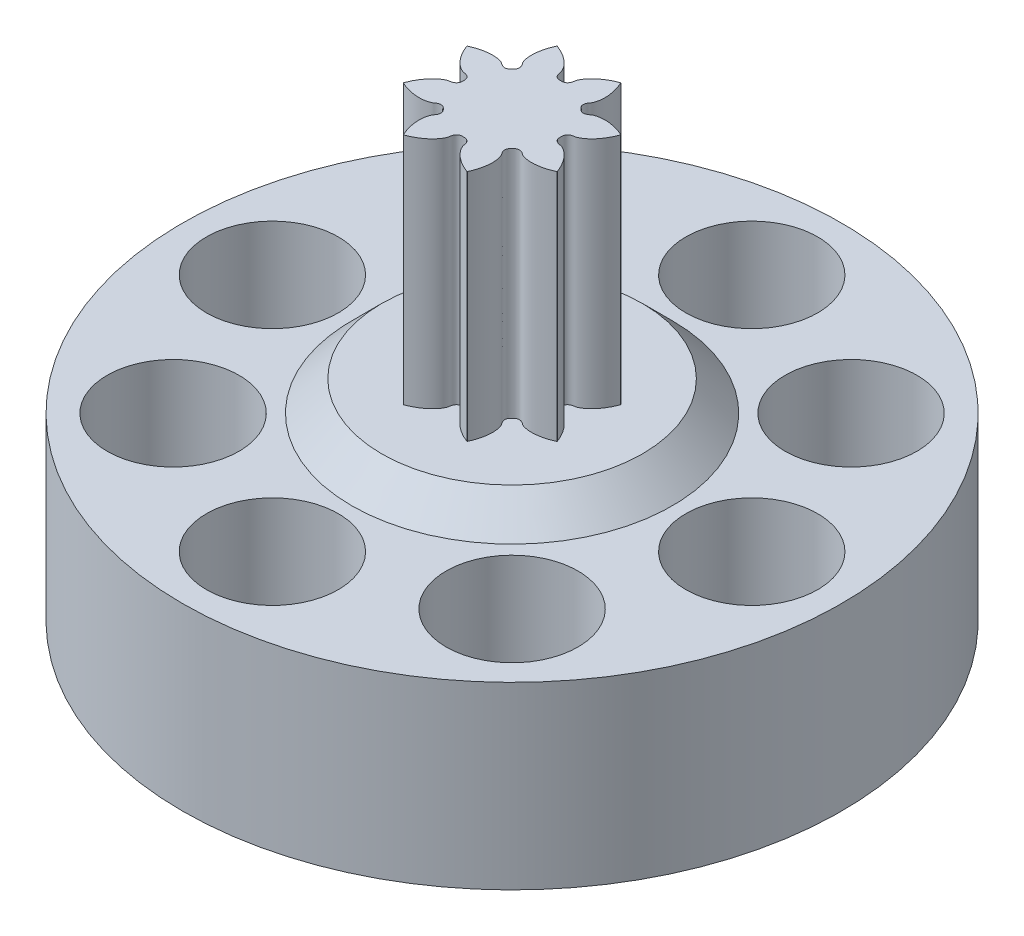
SolidWorks part; units mm, degrees
ref_plane "Front Plane" through (0, 0, 0) normal (0, 0, 1) x (1, 0, 0)
ref_plane "Top Plane" through (0, 0, 0) normal (0, 1, 0) x (1, 0, 0)
ref_plane "Right Plane" through (0, 0, 0) normal (1, 0, 0) x (0, 0, -1)
sketch "Sketch1" plane through (0, 0, 0) normal (0, 1, 0) x (1, 0, 0)
  circle A0 centre (0, 0) radius 11
  dimension "D1" = 22
extrude "Boss-Extrude1" add sketch "Sketch1" along normal mid plane 6
sketch "Sketch2" plane through (0, 3, 0) normal (0, 1, 0) x (1, 0, 0)
  circle A0 centre (0, 8) radius 1
  circle A1 centre (-5.6569, 5.6569) radius 1
  circle A2 centre (5.6569, 5.6569) radius 1
  circle A3 centre (-5.6569, -5.6569) radius 1
  circle A4 centre (5.6569, -5.6569) radius 1
  circle A5 centre (-8, 0) radius 1
  circle A6 centre (0, -8) radius 1
  circle A7 centre (8, 0) radius 1
  circle A8 centre (0, 0) radius 4
  circle A9 centre (0, 0) radius 11
sketch "Sketch5" plane through (0, 3, 0) normal (0, 1, 0) x (1, 0, 0)
  line L0 (2.5656, 1.0576) -> (2.562, 1.0663)
  line L1 (1.0663, 2.562) -> (1.0576, 2.5656)
  line L2 (-1.0576, 2.5656) -> (-1.0663, 2.562)
  line L3 (-2.562, 1.0663) -> (-2.5656, 1.0576)
  line L4 (-2.5656, -1.0576) -> (-2.562, -1.0663)
  line L5 (-1.0663, -2.562) -> (-1.0576, -2.5656)
  line L6 (1.0576, -2.5656) -> (1.0663, -2.562)
  line L7 (2.562, -1.0663) -> (2.5656, -1.0576)
  circle A1 centre (0, 0) radius 2.8
  spline S0 degree 3 poles (2.5656, 1.0576) (2.5467, 1.0063) (2.5127, 0.9243) (2.4586, 0.8162) (2.4108, 0.7326) (2.3616, 0.6567) (2.3117, 0.5883) (2.2618, 0.5274) (2.2125, 0.4736) (2.1645, 0.4267) (2.1184, 0.3865) (2.0746, 0.3524) (2.0339, 0.3241) (1.9966, 0.3012) (1.9632, 0.2831) (1.9342, 0.2695) (1.9099, 0.2596) (1.8905, 0.253) (1.8694, 0.2467) (1.8487, 0.2452) (1.828, 0.2423) (1.8074, 0.2387) (1.7821, 0.2325) (1.7521, 0.2221) (1.7278, 0.2103) (1.7086, 0.1983) (1.6939, 0.1875) (1.6793, 0.1746) (1.665, 0.1592) (1.6515, 0.1408) (1.6395, 0.1191) (1.6301, 0.0941) (1.6246, 0.0677) (1.6231, 0.036) (1.6249, 0) (1.6231, -0.036) (1.6246, -0.0677) (1.6301, -0.0941) (1.6395, -0.1191) (1.6515, -0.1408) (1.665, -0.1592) (1.6793, -0.1746) (1.6982, -0.1913) (1.7224, -0.2076) (1.7521, -0.2221) (1.7821, -0.2325) (1.8074, -0.2387) (1.828, -0.2423) (1.8487, -0.2452) (1.8694, -0.2467) (1.8905, -0.253) (1.9099, -0.2596) (1.9342, -0.2695) (1.9632, -0.2831) (1.9966, -0.3012) (2.0339, -0.3241) (2.0746, -0.3524) (2.1184, -0.3865) (2.1645, -0.4267) (2.2125, -0.4736) (2.2618, -0.5274) (2.3117, -0.5883) (2.3616, -0.6567) (2.4108, -0.7326) (2.4586, -0.8162) (2.5127, -0.9243) (2.5467, -1.0063) (2.5656, -1.0576) knots 0.018496 0.018496 0.018496 0.018496 0.071158 0.103928 0.134826 0.16385 0.191003 0.216283 0.23969 0.261224 0.280886 0.298676 0.314593 0.328637 0.340809 0.351108 0.359535 0.366089 0.37077 0.380767 0.385886 0.390938 0.400931 0.410975 0.421412 0.426928 0.432746 0.438959 0.445665 0.452957 0.460893 0.469469 0.478579 0.486756 0.5 0.513244 0.521421 0.530531 0.539107 0.547043 0.554335 0.561041 0.567254 0.578588 0.589025 0.599069 0.609062 0.614114 0.619233 0.62923 0.633911 0.640465 0.648892 0.659191 0.671363 0.685407 0.701324 0.719114 0.738776 0.76031 0.783717 0.808997 0.83615 0.865174 0.896072 0.928842 0.981504 0.981504 0.981504 0.981504
  spline S1 degree 3 poles (1.0663, 2.562) (1.0892, 2.5123) (1.1232, 2.4303) (1.1614, 2.3156) (1.1867, 2.2227) (1.2056, 2.1343) (1.2186, 2.0507) (1.2264, 1.9723) (1.2296, 1.8994) (1.2288, 1.8323) (1.2246, 1.7712) (1.2178, 1.7162) (1.209, 1.6673) (1.1988, 1.6248) (1.188, 1.5884) (1.1771, 1.5582) (1.1669, 1.534) (1.1579, 1.5157) (1.1474, 1.4963) (1.1339, 1.4806) (1.1212, 1.464) (1.1092, 1.4468) (1.0957, 1.4245) (1.0819, 1.396) (1.0731, 1.3704) (1.0679, 1.3484) (1.0652, 1.3304) (1.0639, 1.3109) (1.0647, 1.2899) (1.0682, 1.2673) (1.0751, 1.2435) (1.0861, 1.2192) (1.1009, 1.1966) (1.1223, 1.1732) (1.149, 1.149) (1.1732, 1.1223) (1.1966, 1.1009) (1.2192, 1.0861) (1.2435, 1.0751) (1.2673, 1.0682) (1.2899, 1.0647) (1.3109, 1.0639) (1.3361, 1.0655) (1.3647, 1.0711) (1.396, 1.0819) (1.4245, 1.0957) (1.4468, 1.1092) (1.464, 1.1212) (1.4806, 1.1339) (1.4963, 1.1474) (1.5157, 1.1579) (1.534, 1.1669) (1.5582, 1.1771) (1.5884, 1.188) (1.6248, 1.1988) (1.6673, 1.209) (1.7162, 1.2178) (1.7712, 1.2246) (1.8323, 1.2288) (1.8994, 1.2296) (1.9723, 1.2264) (2.0507, 1.2186) (2.1343, 1.2056) (2.2227, 1.1867) (2.3156, 1.1614) (2.4303, 1.1232) (2.5123, 1.0892) (2.562, 1.0663) knots 0.018496 0.018496 0.018496 0.018496 0.071158 0.103928 0.134826 0.16385 0.191003 0.216283 0.23969 0.261224 0.280886 0.298676 0.314593 0.328637 0.340809 0.351108 0.359535 0.366089 0.37077 0.380767 0.385886 0.390938 0.400931 0.410975 0.421412 0.426928 0.432746 0.438959 0.445665 0.452957 0.460893 0.469469 0.478579 0.486756 0.5 0.513244 0.521421 0.530531 0.539107 0.547043 0.554335 0.561041 0.567254 0.578588 0.589025 0.599069 0.609062 0.614114 0.619233 0.62923 0.633911 0.640465 0.648892 0.659191 0.671363 0.685407 0.701324 0.719114 0.738776 0.76031 0.783717 0.808997 0.83615 0.865174 0.896072 0.928842 0.981504 0.981504 0.981504 0.981504
  spline S2 degree 3 poles (-1.0576, 2.5656) (-1.0063, 2.5467) (-0.9243, 2.5127) (-0.8162, 2.4586) (-0.7326, 2.4108) (-0.6567, 2.3616) (-0.5883, 2.3117) (-0.5274, 2.2618) (-0.4736, 2.2125) (-0.4267, 2.1645) (-0.3865, 2.1184) (-0.3524, 2.0746) (-0.3241, 2.0339) (-0.3012, 1.9966) (-0.2831, 1.9632) (-0.2695, 1.9342) (-0.2596, 1.9099) (-0.253, 1.8905) (-0.2467, 1.8694) (-0.2452, 1.8487) (-0.2423, 1.828) (-0.2387, 1.8074) (-0.2325, 1.7821) (-0.2221, 1.7521) (-0.2103, 1.7278) (-0.1983, 1.7086) (-0.1875, 1.6939) (-0.1746, 1.6793) (-0.1592, 1.665) (-0.1408, 1.6515) (-0.1191, 1.6395) (-0.0941, 1.6301) (-0.0677, 1.6246) (-0.036, 1.6231) (0, 1.6249) (0.036, 1.6231) (0.0677, 1.6246) (0.0941, 1.6301) (0.1191, 1.6395) (0.1408, 1.6515) (0.1592, 1.665) (0.1746, 1.6793) (0.1913, 1.6982) (0.2076, 1.7224) (0.2221, 1.7521) (0.2325, 1.7821) (0.2387, 1.8074) (0.2423, 1.828) (0.2452, 1.8487) (0.2467, 1.8694) (0.253, 1.8905) (0.2596, 1.9099) (0.2695, 1.9342) (0.2831, 1.9632) (0.3012, 1.9966) (0.3241, 2.0339) (0.3524, 2.0746) (0.3865, 2.1184) (0.4267, 2.1645) (0.4736, 2.2125) (0.5274, 2.2618) (0.5883, 2.3117) (0.6567, 2.3616) (0.7326, 2.4108) (0.8162, 2.4586) (0.9243, 2.5127) (1.0063, 2.5467) (1.0576, 2.5656) knots 0.018496 0.018496 0.018496 0.018496 0.071158 0.103928 0.134826 0.16385 0.191003 0.216283 0.23969 0.261224 0.280886 0.298676 0.314593 0.328637 0.340809 0.351108 0.359535 0.366089 0.37077 0.380767 0.385886 0.390938 0.400931 0.410975 0.421412 0.426928 0.432746 0.438959 0.445665 0.452957 0.460893 0.469469 0.478579 0.486756 0.5 0.513244 0.521421 0.530531 0.539107 0.547043 0.554335 0.561041 0.567254 0.578588 0.589025 0.599069 0.609062 0.614114 0.619233 0.62923 0.633911 0.640465 0.648892 0.659191 0.671363 0.685407 0.701324 0.719114 0.738776 0.76031 0.783717 0.808997 0.83615 0.865174 0.896072 0.928842 0.981504 0.981504 0.981504 0.981504
  spline S3 degree 3 poles (-2.562, 1.0663) (-2.5123, 1.0892) (-2.4303, 1.1232) (-2.3156, 1.1614) (-2.2227, 1.1867) (-2.1343, 1.2056) (-2.0507, 1.2186) (-1.9723, 1.2264) (-1.8994, 1.2296) (-1.8323, 1.2288) (-1.7712, 1.2246) (-1.7162, 1.2178) (-1.6673, 1.209) (-1.6248, 1.1988) (-1.5884, 1.188) (-1.5582, 1.1771) (-1.534, 1.1669) (-1.5157, 1.1579) (-1.4963, 1.1474) (-1.4806, 1.1339) (-1.464, 1.1212) (-1.4468, 1.1092) (-1.4245, 1.0957) (-1.396, 1.0819) (-1.3704, 1.0731) (-1.3484, 1.0679) (-1.3304, 1.0652) (-1.3109, 1.0639) (-1.2899, 1.0647) (-1.2673, 1.0682) (-1.2435, 1.0751) (-1.2192, 1.0861) (-1.1966, 1.1009) (-1.1732, 1.1223) (-1.149, 1.149) (-1.1223, 1.1732) (-1.1009, 1.1966) (-1.0861, 1.2192) (-1.0751, 1.2435) (-1.0682, 1.2673) (-1.0647, 1.2899) (-1.0639, 1.3109) (-1.0655, 1.3361) (-1.0711, 1.3647) (-1.0819, 1.396) (-1.0957, 1.4245) (-1.1092, 1.4468) (-1.1212, 1.464) (-1.1339, 1.4806) (-1.1474, 1.4963) (-1.1579, 1.5157) (-1.1669, 1.534) (-1.1771, 1.5582) (-1.188, 1.5884) (-1.1988, 1.6248) (-1.209, 1.6673) (-1.2178, 1.7162) (-1.2246, 1.7712) (-1.2288, 1.8323) (-1.2296, 1.8994) (-1.2264, 1.9723) (-1.2186, 2.0507) (-1.2056, 2.1343) (-1.1867, 2.2227) (-1.1614, 2.3156) (-1.1232, 2.4303) (-1.0892, 2.5123) (-1.0663, 2.562) knots 0.018496 0.018496 0.018496 0.018496 0.071158 0.103928 0.134826 0.16385 0.191003 0.216283 0.23969 0.261224 0.280886 0.298676 0.314593 0.328637 0.340809 0.351108 0.359535 0.366089 0.37077 0.380767 0.385886 0.390938 0.400931 0.410975 0.421412 0.426928 0.432746 0.438959 0.445665 0.452957 0.460893 0.469469 0.478579 0.486756 0.5 0.513244 0.521421 0.530531 0.539107 0.547043 0.554335 0.561041 0.567254 0.578588 0.589025 0.599069 0.609062 0.614114 0.619233 0.62923 0.633911 0.640465 0.648892 0.659191 0.671363 0.685407 0.701324 0.719114 0.738776 0.76031 0.783717 0.808997 0.83615 0.865174 0.896072 0.928842 0.981504 0.981504 0.981504 0.981504
  spline S4 degree 3 poles (-2.5656, -1.0576) (-2.5467, -1.0063) (-2.5127, -0.9243) (-2.4586, -0.8162) (-2.4108, -0.7326) (-2.3616, -0.6567) (-2.3117, -0.5883) (-2.2618, -0.5274) (-2.2125, -0.4736) (-2.1645, -0.4267) (-2.1184, -0.3865) (-2.0746, -0.3524) (-2.0339, -0.3241) (-1.9966, -0.3012) (-1.9632, -0.2831) (-1.9342, -0.2695) (-1.9099, -0.2596) (-1.8905, -0.253) (-1.8694, -0.2467) (-1.8487, -0.2452) (-1.828, -0.2423) (-1.8074, -0.2387) (-1.7821, -0.2325) (-1.7521, -0.2221) (-1.7278, -0.2103) (-1.7086, -0.1983) (-1.6939, -0.1875) (-1.6793, -0.1746) (-1.665, -0.1592) (-1.6515, -0.1408) (-1.6395, -0.1191) (-1.6301, -0.0941) (-1.6246, -0.0677) (-1.6231, -0.036) (-1.6249, 0) (-1.6231, 0.036) (-1.6246, 0.0677) (-1.6301, 0.0941) (-1.6395, 0.1191) (-1.6515, 0.1408) (-1.665, 0.1592) (-1.6793, 0.1746) (-1.6982, 0.1913) (-1.7224, 0.2076) (-1.7521, 0.2221) (-1.7821, 0.2325) (-1.8074, 0.2387) (-1.828, 0.2423) (-1.8487, 0.2452) (-1.8694, 0.2467) (-1.8905, 0.253) (-1.9099, 0.2596) (-1.9342, 0.2695) (-1.9632, 0.2831) (-1.9966, 0.3012) (-2.0339, 0.3241) (-2.0746, 0.3524) (-2.1184, 0.3865) (-2.1645, 0.4267) (-2.2125, 0.4736) (-2.2618, 0.5274) (-2.3117, 0.5883) (-2.3616, 0.6567) (-2.4108, 0.7326) (-2.4586, 0.8162) (-2.5127, 0.9243) (-2.5467, 1.0063) (-2.5656, 1.0576) knots 0.018496 0.018496 0.018496 0.018496 0.071158 0.103928 0.134826 0.16385 0.191003 0.216283 0.23969 0.261224 0.280886 0.298676 0.314593 0.328637 0.340809 0.351108 0.359535 0.366089 0.37077 0.380767 0.385886 0.390938 0.400931 0.410975 0.421412 0.426928 0.432746 0.438959 0.445665 0.452957 0.460893 0.469469 0.478579 0.486756 0.5 0.513244 0.521421 0.530531 0.539107 0.547043 0.554335 0.561041 0.567254 0.578588 0.589025 0.599069 0.609062 0.614114 0.619233 0.62923 0.633911 0.640465 0.648892 0.659191 0.671363 0.685407 0.701324 0.719114 0.738776 0.76031 0.783717 0.808997 0.83615 0.865174 0.896072 0.928842 0.981504 0.981504 0.981504 0.981504
  spline S5 degree 3 poles (-1.0663, -2.562) (-1.0892, -2.5123) (-1.1232, -2.4303) (-1.1614, -2.3156) (-1.1867, -2.2227) (-1.2056, -2.1343) (-1.2186, -2.0507) (-1.2264, -1.9723) (-1.2296, -1.8994) (-1.2288, -1.8323) (-1.2246, -1.7712) (-1.2178, -1.7162) (-1.209, -1.6673) (-1.1988, -1.6248) (-1.188, -1.5884) (-1.1771, -1.5582) (-1.1669, -1.534) (-1.1579, -1.5157) (-1.1474, -1.4963) (-1.1339, -1.4806) (-1.1212, -1.464) (-1.1092, -1.4468) (-1.0957, -1.4245) (-1.0819, -1.396) (-1.0731, -1.3704) (-1.0679, -1.3484) (-1.0652, -1.3304) (-1.0639, -1.3109) (-1.0647, -1.2899) (-1.0682, -1.2673) (-1.0751, -1.2435) (-1.0861, -1.2192) (-1.1009, -1.1966) (-1.1223, -1.1732) (-1.149, -1.149) (-1.1732, -1.1223) (-1.1966, -1.1009) (-1.2192, -1.0861) (-1.2435, -1.0751) (-1.2673, -1.0682) (-1.2899, -1.0647) (-1.3109, -1.0639) (-1.3361, -1.0655) (-1.3647, -1.0711) (-1.396, -1.0819) (-1.4245, -1.0957) (-1.4468, -1.1092) (-1.464, -1.1212) (-1.4806, -1.1339) (-1.4963, -1.1474) (-1.5157, -1.1579) (-1.534, -1.1669) (-1.5582, -1.1771) (-1.5884, -1.188) (-1.6248, -1.1988) (-1.6673, -1.209) (-1.7162, -1.2178) (-1.7712, -1.2246) (-1.8323, -1.2288) (-1.8994, -1.2296) (-1.9723, -1.2264) (-2.0507, -1.2186) (-2.1343, -1.2056) (-2.2227, -1.1867) (-2.3156, -1.1614) (-2.4303, -1.1232) (-2.5123, -1.0892) (-2.562, -1.0663) knots 0.018496 0.018496 0.018496 0.018496 0.071158 0.103928 0.134826 0.16385 0.191003 0.216283 0.23969 0.261224 0.280886 0.298676 0.314593 0.328637 0.340809 0.351108 0.359535 0.366089 0.37077 0.380767 0.385886 0.390938 0.400931 0.410975 0.421412 0.426928 0.432746 0.438959 0.445665 0.452957 0.460893 0.469469 0.478579 0.486756 0.5 0.513244 0.521421 0.530531 0.539107 0.547043 0.554335 0.561041 0.567254 0.578588 0.589025 0.599069 0.609062 0.614114 0.619233 0.62923 0.633911 0.640465 0.648892 0.659191 0.671363 0.685407 0.701324 0.719114 0.738776 0.76031 0.783717 0.808997 0.83615 0.865174 0.896072 0.928842 0.981504 0.981504 0.981504 0.981504
  spline S6 degree 3 poles (1.0576, -2.5656) (1.0063, -2.5467) (0.9243, -2.5127) (0.8162, -2.4586) (0.7326, -2.4108) (0.6567, -2.3616) (0.5883, -2.3117) (0.5274, -2.2618) (0.4736, -2.2125) (0.4267, -2.1645) (0.3865, -2.1184) (0.3524, -2.0746) (0.3241, -2.0339) (0.3012, -1.9966) (0.2831, -1.9632) (0.2695, -1.9342) (0.2596, -1.9099) (0.253, -1.8905) (0.2467, -1.8694) (0.2452, -1.8487) (0.2423, -1.828) (0.2387, -1.8074) (0.2325, -1.7821) (0.2221, -1.7521) (0.2103, -1.7278) (0.1983, -1.7086) (0.1875, -1.6939) (0.1746, -1.6793) (0.1592, -1.665) (0.1408, -1.6515) (0.1191, -1.6395) (0.0941, -1.6301) (0.0677, -1.6246) (0.036, -1.6231) (0, -1.6249) (-0.036, -1.6231) (-0.0677, -1.6246) (-0.0941, -1.6301) (-0.1191, -1.6395) (-0.1408, -1.6515) (-0.1592, -1.665) (-0.1746, -1.6793) (-0.1913, -1.6982) (-0.2076, -1.7224) (-0.2221, -1.7521) (-0.2325, -1.7821) (-0.2387, -1.8074) (-0.2423, -1.828) (-0.2452, -1.8487) (-0.2467, -1.8694) (-0.253, -1.8905) (-0.2596, -1.9099) (-0.2695, -1.9342) (-0.2831, -1.9632) (-0.3012, -1.9966) (-0.3241, -2.0339) (-0.3524, -2.0746) (-0.3865, -2.1184) (-0.4267, -2.1645) (-0.4736, -2.2125) (-0.5274, -2.2618) (-0.5883, -2.3117) (-0.6567, -2.3616) (-0.7326, -2.4108) (-0.8162, -2.4586) (-0.9243, -2.5127) (-1.0063, -2.5467) (-1.0576, -2.5656) knots 0.018496 0.018496 0.018496 0.018496 0.071158 0.103928 0.134826 0.16385 0.191003 0.216283 0.23969 0.261224 0.280886 0.298676 0.314593 0.328637 0.340809 0.351108 0.359535 0.366089 0.37077 0.380767 0.385886 0.390938 0.400931 0.410975 0.421412 0.426928 0.432746 0.438959 0.445665 0.452957 0.460893 0.469469 0.478579 0.486756 0.5 0.513244 0.521421 0.530531 0.539107 0.547043 0.554335 0.561041 0.567254 0.578588 0.589025 0.599069 0.609062 0.614114 0.619233 0.62923 0.633911 0.640465 0.648892 0.659191 0.671363 0.685407 0.701324 0.719114 0.738776 0.76031 0.783717 0.808997 0.83615 0.865174 0.896072 0.928842 0.981504 0.981504 0.981504 0.981504
  spline S7 degree 3 poles (2.562, -1.0663) (2.5123, -1.0892) (2.4303, -1.1232) (2.3156, -1.1614) (2.2227, -1.1867) (2.1343, -1.2056) (2.0507, -1.2186) (1.9723, -1.2264) (1.8994, -1.2296) (1.8323, -1.2288) (1.7712, -1.2246) (1.7162, -1.2178) (1.6673, -1.209) (1.6248, -1.1988) (1.5884, -1.188) (1.5582, -1.1771) (1.534, -1.1669) (1.5157, -1.1579) (1.4963, -1.1474) (1.4806, -1.1339) (1.464, -1.1212) (1.4468, -1.1092) (1.4245, -1.0957) (1.396, -1.0819) (1.3704, -1.0731) (1.3484, -1.0679) (1.3304, -1.0652) (1.3109, -1.0639) (1.2899, -1.0647) (1.2673, -1.0682) (1.2435, -1.0751) (1.2192, -1.0861) (1.1966, -1.1009) (1.1732, -1.1223) (1.149, -1.149) (1.1223, -1.1732) (1.1009, -1.1966) (1.0861, -1.2192) (1.0751, -1.2435) (1.0682, -1.2673) (1.0647, -1.2899) (1.0639, -1.3109) (1.0655, -1.3361) (1.0711, -1.3647) (1.0819, -1.396) (1.0957, -1.4245) (1.1092, -1.4468) (1.1212, -1.464) (1.1339, -1.4806) (1.1474, -1.4963) (1.1579, -1.5157) (1.1669, -1.534) (1.1771, -1.5582) (1.188, -1.5884) (1.1988, -1.6248) (1.209, -1.6673) (1.2178, -1.7162) (1.2246, -1.7712) (1.2288, -1.8323) (1.2296, -1.8994) (1.2264, -1.9723) (1.2186, -2.0507) (1.2056, -2.1343) (1.1867, -2.2227) (1.1614, -2.3156) (1.1232, -2.4303) (1.0892, -2.5123) (1.0663, -2.562) knots 0.018496 0.018496 0.018496 0.018496 0.071158 0.103928 0.134826 0.16385 0.191003 0.216283 0.23969 0.261224 0.280886 0.298676 0.314593 0.328637 0.340809 0.351108 0.359535 0.366089 0.37077 0.380767 0.385886 0.390938 0.400931 0.410975 0.421412 0.426928 0.432746 0.438959 0.445665 0.452957 0.460893 0.469469 0.478579 0.486756 0.5 0.513244 0.521421 0.530531 0.539107 0.547043 0.554335 0.561041 0.567254 0.578588 0.589025 0.599069 0.609062 0.614114 0.619233 0.62923 0.633911 0.640465 0.648892 0.659191 0.671363 0.685407 0.701324 0.719114 0.738776 0.76031 0.783717 0.808997 0.83615 0.865174 0.896072 0.928842 0.981504 0.981504 0.981504 0.981504
  dimension "D2" = 5.6
extrude "Boss-Extrude2" add sketch "Sketch5" along normal blind 8.8 contours S7 L7 S0 L0 S1 L1 S2 L2 S3 L3 S4 L4 S5 L5 S6 L6 region at (0, 3, 0)
hole_wizard "CBORE for M2 SHCS3" positions "Sketch11" profile "Sketch13" counterbore size "M2" standard "ANSI Metric"
sketch "Sketch11" plane through (0, 3, 0) normal (0, 1, 0) x (1, 0, 0)
  point P0 (-8, 0)
  point P3 (-5.6569, 5.6569)
  point P6 (0, 8)
  point P9 (5.6569, 5.6569)
  point P12 (8, 0)
  point P15 (5.6569, -5.6569)
  point P18 (0, -8)
  point P21 (-5.6569, -5.6569)
sketch "Sketch13" plane through (-8, 3, 0) normal (1, 0, 0) x (0, 0, 1)
  line L0 (0, 0) -> (0, 6.7811)
  line L1 (0, 6.7811) -> (1.3, 6)
  line L2 (1.3, 6) -> (1.3, 5)
  line L3 (1.3, 5) -> (2.2, 5)
  line L4 (2.2, 5) -> (2.2, 0)
  line L5 (2.2, 0) -> (0, 0)
  line L10 (0, 6.7811) -> (-1.3, 6) construction
  line L11 (0, -6.35) -> (0, 107.95) construction
  dimension "Hole Dia." = 2.6
  dimension "Hole Depth" = 6
  dimension "C'Bore Dia." = 4.4
  dimension "C'Bore Depth" = 5
  dimension "Drill Angle" = 118
sketch "Sketch14" plane through (0, -3, 0) normal (0, -1, 0) x (1, 0, 0)
  circle A0 centre (0, 0) radius 4.3
  dimension "D1" = 8.6
extrude "Cut-Extrude4" cut sketch "Sketch14" against normal blind 5.95
sketch "Sketch15" plane through (0, 3, 0) normal (0, 1, 0) x (1, 0, 0)
  circle A0 centre (0, 0) radius 4.35
  dimension "D1" = 8.7
extrude "Boss-Extrude4" add sketch "Sketch15" along normal blind 1
chamfer "Chamfer1" distance 1 angle 45 1 edges at (0, 3, 4.35)
